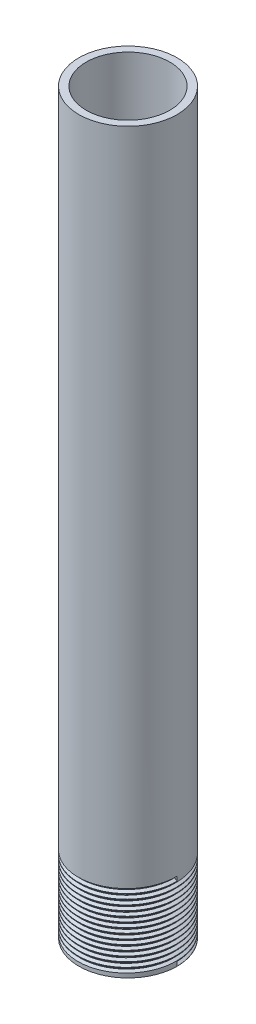
SolidWorks part; units mm, degrees
material "Cast Alloy Steel"
ref_plane "Front Plane" through (0, 0, 0) normal (0, 0, 1) x (1, 0, 0)
ref_plane "Top Plane" through (0, 0, 0) normal (0, 1, 0) x (1, 0, 0)
ref_plane "Right Plane" through (0, 0, 0) normal (1, 0, 0) x (0, 0, -1)
sketch "Sketch1" plane through (0, 0, 0) normal (0, 1, 0) x (1, 0, 0)
  circle A0 centre (0, 0) radius 10
  circle A1 centre (0, 0) radius 8.5
  dimension "D1" = 20
  dimension "D2" = 17
extrude "Boss-Extrude1" add sketch "Sketch1" along normal blind 150
thread "Thread1" pitch 1 method cut profile "Thread Profile2" start angle 0, offset 0, length 15, pitch 1, diameter 20
ref_plane "Plane2" through (10, 0, 0) normal (0, 0, 1) x (1, 0, 0)
sketch "Thread Profile2" plane through (10, 0, 0) normal (0, 0, 1) x (1, 0, 0)
  line L0 (0, 0) -> (0, 1) construction
  line L11 (0, 0) -> (0, 0.875)
  line L12 (0, 0.875) -> (-0.5413, 0.5625)
  line L13 (-0.5413, 0.5625) -> (-0.5413, 0.3125)
  line L15 (-0.5413, 0.3125) -> (0, 0)
  line L17 (-0.5413, 0.4375) -> (0, 0.4375) construction
  point P2 (0, 0)
  dimension "Pitch" = 1
  dimension "Profile_Angle" = 60
  dimension "Profile_Land" = 0.25
  dimension "Profile_Height" = 0.5413
